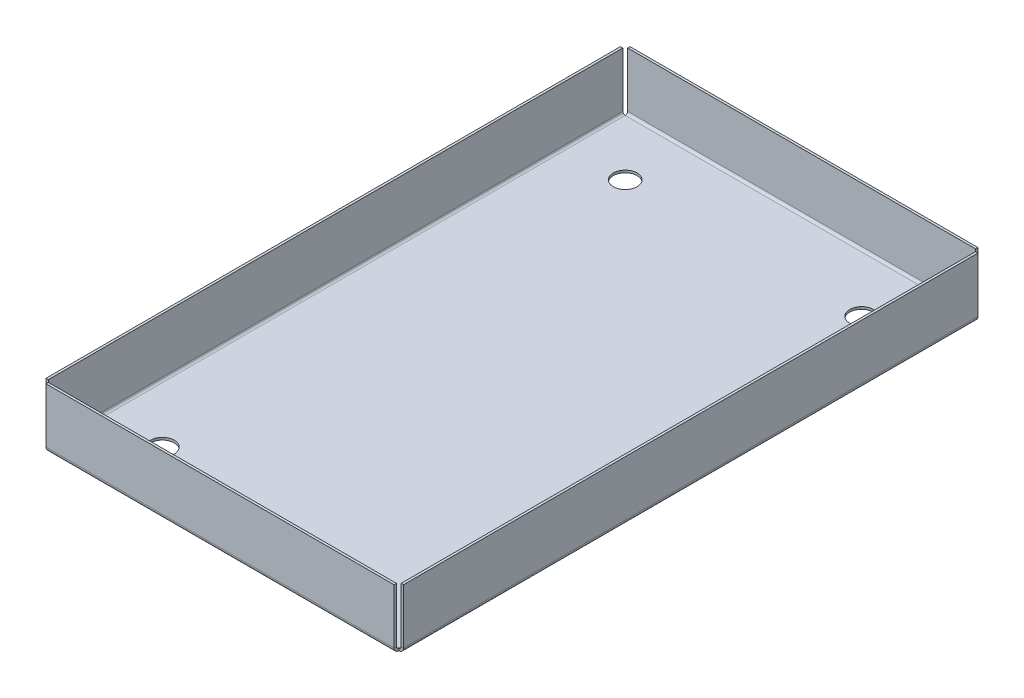
SolidWorks part; units mm, degrees
note: The reader was unsure of these and kept them because the rebuilt part matched: thickness of "Base-Flange1", "Edge-Flange1", "Edge-Flange2", "Edge-Flange3", "Edge-Flange4", "Sheet-Metal1", "Sheet-Metal2", "Sheet-Metal3", "Sheet-Metal4", "Sheet-Metal5", "Sheet-Metal6", "Sheet-Metal7", "Sheet-Metal17"; flange length of "Edge-Flange1", "Edge-Flange2", "Edge-Flange3", "Edge-Flange4".
ref_plane "Front Plane" through (0, 0, 0) normal (0, 0, 1) x (1, 0, 0)
ref_plane "Top Plane" through (0, 0, 0) normal (0, 1, 0) x (1, 0, 0)
ref_plane "Right Plane" through (0, 0, 0) normal (1, 0, 0) x (0, 0, -1)
sketch "Sketch1" plane through (0, 0, 0) normal (0, 1, 0) x (1, 0, 0)
  line L1 (-7.3, 12.05) -> (7.3, 12.05)
  line L2 (-7.3, 12.05) -> (-7.3, -12.05)
  line L3 (-7.3, -12.05) -> (7.3, -12.05)
  line L4 (7.3, 12.05) -> (7.3, -12.05)
  line L5 (-7.3, 12.05) -> (7.3, -12.05) construction
  line L6 (-7.3, -12.05) -> (7.3, 12.05) construction
  point P0 (0, 0)
  dimension "D1" = 24.1
  dimension "D2" = 14.6
base flange "Base-Flange1" sketch "Sketch1" thickness 0.1 reverse thickness direction no parameters "D1"=0.7366
edge flange "Edge-Flange1" sketch "Sketch10" flange angle 90 flange length 2.5 flange position bend outside bend radius 0.1 thickness 0.1 relief rectangular parameters "D6"=10
sketch "Sketch10" plane through (0, 0, 12.05) normal (0, 0, 1) x (1, 0, 0)
  line L0 (-7.3, 0) -> (7.3, 0) construction
  line L1 (-7.3, 0) -> (7.3, 0)
  line L2 (-7.3, 0) -> (-7.3, 2.4)
  line L3 (-7.3, 2.4) -> (7.3, 2.4)
  line L4 (7.3, 2.4) -> (7.3, 0)
bend "EdgeBend1" bend radius 0.1 bend angle 90 parameters "D5"=1
edge flange "Edge-Flange2" sketch "Sketch13" flange angle 90 flange length 2.5 flange position bend outside bend radius 0.1 thickness 0.1 relief rectangular parameters "D6"=10
sketch "Sketch13" plane through (0, 0, -12.05) normal (0, 0, -1) x (-1, 0, 0)
  line L0 (-7.3, 0) -> (7.3, 0) construction
  line L1 (-7.3, 0) -> (7.3, 0)
  line L2 (-7.3, 0) -> (-7.3, 2.4)
  line L3 (-7.3, 2.4) -> (7.3, 2.4)
  line L4 (7.3, 2.4) -> (7.3, 0)
bend "EdgeBend2" bend radius 0.1 bend angle 90 parameters "D5"=2
edge flange "Edge-Flange3" sketch "Sketch16" flange angle 90 flange length 2.5 flange position bend outside bend radius 0.1 thickness 0.1 relief rectangular parameters "D6"=10
sketch "Sketch16" plane through (7.3, 0, 0) normal (1, 0, 0) x (0, 0, -1)
  line L0 (-12.05, 0) -> (12.05, 0) construction
  line L1 (-12.05, 0) -> (12.05, 0)
  line L2 (-12.05, 0) -> (-12.05, 2.4)
  line L3 (-12.05, 2.4) -> (12.05, 2.4)
  line L4 (12.05, 2.4) -> (12.05, 0)
bend "EdgeBend3" bend radius 0.1 bend angle 90 parameters "D5"=3
edge flange "Edge-Flange4" sketch "Sketch21" flange angle 90 flange length 2.5 flange position bend outside bend radius 0.1 thickness 0.1 relief rectangular parameters "D6"=10
sketch "Sketch21" plane through (-7.3, 0, 0) normal (-1, 0, 0) x (0, 0, 1)
  line L2 (-12.05, 0) -> (-12.05, 2.4)
  line L3 (-12.05, 2.4) -> (12.05, 2.4)
  line L4 (12.05, 2.4) -> (12.05, 0)
  line L5 (-12.05, 0) -> (12.05, 0) construction
  line L6 (-12.05, 0) -> (12.05, 0)
bend "EdgeBend4" bend radius 0.1 bend angle 90 parameters "D5"=4
sketch "Sketch23" plane through (0, -0.1, 0) normal (0, -1, 0) x (1, 0, 0)
  line L0 (-7.5, 12.05) -> (-7.5, -12.05) construction
  line L1 (7.3, 12.25) -> (-7.3, 12.25) construction
  line L2 (0, 0) -> (-13.5156, 0) construction
  line L3 (0, 0) -> (0, -13.6288) construction
  circle A0 centre (-4.96, 9.71) radius 0.5
  circle A1 centre (-4.96, -9.71) radius 0.5
  circle A2 centre (4.96, -9.71) radius 0.5
  dimension "D1" = 1
  dimension "D2" = 2.54
  dimension "D3" = 2.54
extrude "Cut-Extrude1" cut sketch "Sketch23" against normal blind 10 normal cut yes
sketch "Sketch24" plane through (0, -0.1, 0) normal (0, -1, 0) x (1, 0, 0)
  line L1 (-1.7162, 8.2997) -> (-1.7162, -6.7416) construction
  line L2 (-3.9171, 8.2997) -> (-3.9171, -6.7416) construction
  text T0 "RN2483" font "Arial Narrow" height 1.4
  text T1 "########" font "Arial Narrow" height 1.2
extrude "Boss-Extrude2" add sketch "Sketch24" along normal blind 0.01 separate body
sketch "Sketch26" plane through (0, -0.1, 0) normal (0, -1, 0) x (1, 0, 0)
  line L4 (1.6101, 2.1924) -> (2.7319, 2.0303)
  line L5 (2.7724, 1.5974) -> (2.0967, 1.1781)
  line L6 (2.0967, 1.1781) -> (2.7724, 0.7858)
  line L7 (2.7319, 0.3394) -> (1.6101, 0.1636)
  line L8 (1.6101, 0.1636) -> (1.6101, 0.5288)
  line L9 (1.6101, 0.5288) -> (2.3669, 0.6235)
  line L10 (2.3669, 0.6235) -> (1.7588, 0.9752)
  line L11 (1.7588, 1.3945) -> (2.3805, 1.7462)
  line L12 (2.3805, 1.7462) -> (1.6101, 1.8409)
  line L13 (1.6101, 1.8409) -> (1.6101, 2.1924)
  line L14 (1.6101, 0.0013) -> (1.6101, -0.3098)
  line L15 (1.6101, -0.3098) -> (2.5562, -0.3098)
  line L16 (2.5562, -0.3098) -> (2.5562, 0.0013)
  line L17 (2.5562, 0.0013) -> (1.6101, 0.0013)
  line L18 (2.3129, -1.7301) -> (2.4481, -1.7301)
  line L19 (2.5697, -1.5814) -> (2.5697, -0.7968)
  line L20 (2.3399, -0.4992) -> (1.8129, -0.4992)
  line L21 (1.6101, -0.7562) -> (1.6101, -1.5814)
  line L22 (1.7588, -1.7437) -> (1.8669, -1.7437)
  line L23 (1.8669, -1.7437) -> (1.8669, -0.9188)
  line L24 (2.0021, -0.7968) -> (2.1642, -0.7968)
  line L25 (2.3129, -0.9188) -> (2.3129, -1.7301)
  line L27 (1.8534, -2.5282) -> (1.8534, -2.7311)
  line L28 (1.7588, -2.8393) -> (1.6101, -2.8393)
  line L29 (1.6101, -2.8393) -> (1.6101, -3.1234)
  line L30 (1.6101, -3.1234) -> (1.8399, -3.1234)
  line L31 (2.1372, -3.1369) -> (2.3669, -3.1369)
  line L32 (2.5697, -2.9476) -> (2.5697, -2.5282)
  line L34 (2.3264, -2.5282) -> (2.3264, -2.7852)
  line L35 (2.2453, -2.8529) -> (2.1642, -2.8529)
  line L36 (2.0967, -2.7717) -> (2.0967, -2.5282)
  line L38 (2.5697, -2.5282) -> (2.5697, -1.906)
  line L39 (2.5697, -1.906) -> (1.6101, -1.906)
  line L40 (1.6101, -1.906) -> (1.6101, -2.1901)
  line L41 (1.6101, -2.1901) -> (1.8534, -2.2036)
  line L42 (1.8534, -2.2036) -> (1.8534, -2.5282)
  line L44 (2.0967, -2.5282) -> (2.0967, -2.1901)
  line L45 (2.0967, -2.1901) -> (2.3264, -2.2036)
  line L46 (2.3264, -2.2036) -> (2.3264, -2.5282)
  line L48 (1.6101, -3.962) -> (1.6101, -4.3408)
  line L49 (1.8399, -4.6114) -> (2.3264, -4.6114)
  line L50 (2.5832, -4.3137) -> (2.5832, -3.962)
  line L52 (2.3264, -3.962) -> (2.3264, -4.1785)
  line L53 (2.2183, -4.2867) -> (1.948, -4.2867)
  line L54 (1.8669, -4.192) -> (1.8669, -3.962)
  line L56 (2.5832, -3.962) -> (2.5832, -3.5833)
  line L57 (2.3534, -3.2993) -> (1.8399, -3.2993)
  line L58 (1.6101, -3.5563) -> (1.6101, -3.962)
  line L60 (1.8669, -3.962) -> (1.8669, -3.7186)
  line L61 (1.948, -3.6239) -> (2.2183, -3.6239)
  line L62 (2.3264, -3.7591) -> (2.3264, -3.962)
  line L63 (1.9615, -7.0597) -> (1.9615, -6.478)
  line L64 (1.9615, -6.478) -> (1.975, -6.478)
  line L65 (1.975, -6.478) -> (1.6101, -6.478)
  line L66 (1.6101, -6.478) -> (1.6101, -6.1669)
  line L67 (1.6101, -6.1669) -> (2.5697, -6.1669)
  line L68 (2.5697, -6.1669) -> (2.5697, -6.478)
  line L69 (2.5697, -6.478) -> (2.2318, -6.478)
  line L70 (2.2318, -6.478) -> (2.2318, -7.0597)
  line L71 (2.2318, -7.0597) -> (2.5697, -7.0597)
  line L72 (2.5697, -7.0597) -> (2.5697, -7.3844)
  line L73 (2.5697, -7.3844) -> (1.6101, -7.3844)
  line L74 (1.6101, -7.3844) -> (1.6101, -7.0597)
  line L75 (1.6101, -7.0597) -> (1.975, -7.0597)
  line L76 (1.975, -7.0597) -> (1.9615, -7.0597)
  line L78 (1.8534, -8.6964) -> (1.8534, -9.1157)
  line L79 (2.0832, -9.3321) -> (2.3129, -9.3321)
  line L80 (2.5562, -9.0887) -> (2.5562, -8.6964)
  line L82 (2.3264, -8.6964) -> (2.3264, -8.9669)
  line L83 (2.2453, -9.0346) -> (2.1642, -9.0346)
  line L84 (2.0832, -8.9534) -> (2.0832, -8.6964)
  line L86 (2.5562, -8.6964) -> (2.5562, -8.0742)
  line L87 (2.5562, -8.0742) -> (1.6101, -8.0742)
  line L88 (1.6101, -8.0742) -> (1.6101, -8.3717)
  line L89 (1.6101, -8.3717) -> (1.8534, -8.3717)
  line L90 (1.8534, -8.3717) -> (1.8534, -8.6964)
  line L92 (2.0832, -8.6964) -> (2.0832, -8.3717)
  line L93 (2.0832, -8.3717) -> (2.3264, -8.3583)
  line L94 (2.3264, -8.3583) -> (2.3264, -8.6964)
  line L95 (2.1053, 5.4392) -> (2.7319, 5.0088)
  line L96 (2.7319, 5.0088) -> (4.7593, 6.2754)
  line L97 (4.7593, 6.7058) -> (4.1447, 7.1485)
  line L98 (4.1447, 7.1485) -> (2.1053, 5.8573)
  line L99 (1.7612, 3.9759) -> (4.1325, 5.4884)
  line L100 (4.1325, 5.4884) -> (4.7714, 5.0211)
  line L101 (4.7714, 4.6153) -> (2.7319, 3.3241)
  line L102 (3.2847, 3.2135) -> (5.5945, 4.6768)
  line L103 (2.8547, 8.0831) -> (3.8499, 7.3575)
  line L104 (3.8499, 7.3575) -> (3.0759, 6.8534)
  line L105 (2.7319, 6.8534) -> (1.8473, 7.4928)
  line L106 (2.3129, -5.9911) -> (2.4481, -5.9911)
  line L107 (2.5697, -5.8424) -> (2.5697, -5.0577)
  line L108 (2.3399, -4.7601) -> (1.8129, -4.7601)
  line L109 (1.6101, -5.0171) -> (1.5966, -5.8424)
  line L110 (1.7588, -6.0046) -> (1.8534, -6.0046)
  line L111 (1.8534, -6.0046) -> (1.8534, -5.1794)
  line L112 (1.9885, -5.0577) -> (2.1642, -5.0577)
  line L113 (2.3129, -5.1794) -> (2.3129, -5.9911)
  line L114 (1.6101, -7.5602) -> (1.6101, -7.8713)
  line L115 (1.6101, -7.8713) -> (2.5562, -7.8713)
  line L116 (2.5562, -7.8713) -> (2.5562, -7.5602)
  line L117 (2.5562, -7.5602) -> (1.6101, -7.5602)
  spline S0 degree 3 poles (2.7319, 2.0303) (2.9211, 1.9897) (2.9481, 1.7327) (2.7724, 1.5974) knots 0 0 0 0 1 1 1 1
  spline S1 degree 3 poles (2.7724, 0.7858) (2.894, 0.6776) (2.9481, 0.4747) (2.7319, 0.3394) knots 0 0 0 0 1 1 1 1
  spline S2 degree 3 poles (1.7588, 0.9752) (1.6372, 1.0561) (1.6237, 1.2863) (1.7588, 1.3945) knots 0 0 0 0 1 1 1 1
  spline S3 degree 3 poles (2.4481, -1.7301) (2.5291, -1.7301) (2.5697, -1.676) (2.5697, -1.5814) knots 0 0 0 0 1 1 1 1
  spline S4 degree 3 poles (2.5697, -0.7968) (2.5697, -0.648) (2.4345, -0.4992) (2.3399, -0.4992) knots 0 0 0 0 1 1 1 1
  spline S5 degree 3 poles (1.8129, -0.4992) (1.7453, -0.4992) (1.6101, -0.6074) (1.6101, -0.7562) knots 0 0 0 0 1 1 1 1
  spline S6 degree 3 poles (1.6101, -1.5814) (1.5966, -1.676) (1.6642, -1.7437) (1.7588, -1.7437) knots 0 0 0 0 1 1 1 1
  spline S7 degree 3 poles (1.8669, -0.9188) (1.8534, -0.8374) (1.921, -0.7968) (2.0021, -0.7968) knots 0 0 0 0 1 1 1 1
  spline S8 degree 3 poles (2.1642, -0.7968) (2.2318, -0.7968) (2.3129, -0.8509) (2.3129, -0.9188) knots 0 0 0 0 1 1 1 1
  spline S9 degree 3 poles (1.8534, -2.7311) (1.8534, -2.7852) (1.8264, -2.8258) (1.7588, -2.8393) knots 0 0 0 0 1 1 1 1
  spline S10 degree 2 poles (1.8399, -3.1234) (1.9615, -3.1234) (1.9885, -3.0017) knots 0 0 0 1 1 1
  spline S11 degree 2 poles (1.9885, -3.0017) (2.0426, -3.1234) (2.1372, -3.1369) knots 0 0 0 1 1 1
  spline S12 degree 3 poles (2.3669, -3.1369) (2.4751, -3.1234) (2.5562, -3.0289) (2.5697, -2.9476) knots 0 0 0 0 1 1 1 1
  spline S13 degree 3 poles (2.3264, -2.7852) (2.3264, -2.8123) (2.2859, -2.8529) (2.2453, -2.8529) knots 0 0 0 0 1 1 1 1
  spline S14 degree 3 poles (2.1642, -2.8529) (2.1237, -2.8529) (2.0967, -2.8258) (2.0967, -2.7717) knots 0 0 0 0 1 1 1 1
  spline S15 degree 3 poles (1.6101, -4.3408) (1.6101, -4.4625) (1.7047, -4.6114) (1.8399, -4.6114) knots 0 0 0 0 1 1 1 1
  spline S16 degree 3 poles (2.3264, -4.6114) (2.4481, -4.6114) (2.5832, -4.476) (2.5832, -4.3137) knots 0 0 0 0 1 1 1 1
  spline S17 degree 3 poles (2.3264, -4.1785) (2.3264, -4.2461) (2.2724, -4.2867) (2.2183, -4.2867) knots 0 0 0 0 1 1 1 1
  spline S18 degree 3 poles (1.948, -4.2867) (1.8804, -4.2867) (1.8669, -4.2461) (1.8669, -4.192) knots 0 0 0 0 1 1 1 1
  spline S19 degree 3 poles (2.5832, -3.5833) (2.5832, -3.4482) (2.4751, -3.2993) (2.3534, -3.2993) knots 0 0 0 0 1 1 1 1
  spline S20 degree 3 poles (1.8399, -3.2993) (1.7183, -3.2993) (1.6101, -3.4075) (1.6101, -3.5563) knots 0 0 0 0 1 1 1 1
  spline S21 degree 3 poles (1.8669, -3.7186) (1.8669, -3.6645) (1.8804, -3.6239) (1.948, -3.6239) knots 0 0 0 0 1 1 1 1
  spline S22 degree 3 poles (2.2183, -3.6239) (2.2859, -3.6239) (2.3264, -3.6915) (2.3264, -3.7591) knots 0 0 0 0 1 1 1 1
  spline S23 degree 3 poles (1.8534, -9.1157) (1.8534, -9.2104) (1.975, -9.3321) (2.0832, -9.3321) knots 0 0 0 0 1 1 1 1
  spline S24 degree 3 poles (2.3129, -9.3321) (2.4345, -9.3321) (2.5562, -9.224) (2.5562, -9.0887) knots 0 0 0 0 1 1 1 1
  spline S25 degree 3 poles (2.3264, -8.9669) (2.3264, -9.0075) (2.2859, -9.0346) (2.2453, -9.0346) knots 0 0 0 0 1 1 1 1
  spline S26 degree 3 poles (2.1642, -9.0346) (2.1237, -9.0346) (2.0832, -9.0075) (2.0832, -8.9534) knots 0 0 0 0 1 1 1 1
  spline S27 degree 2 poles (2.1053, 5.8573) (1.7612, 5.6605) (2.1053, 5.4392) knots 0 0 0 1 1 1
  spline S28 degree 2 poles (4.7593, 6.2754) (5.0294, 6.4722) (4.7593, 6.7058) knots 0 0 0 1 1 1
  spline S29 degree 3 poles (1.1224, 5.6851) (1.1224, 5.0211) (1.3681, 4.4186) (1.7612, 3.9759) knots 0 0 0 0 1 1 1 1
  spline S30 degree 2 poles (4.7714, 5.0211) (5.0294, 4.8242) (4.7714, 4.6153) knots 0 0 0 1 1 1
  spline S31 degree 3 poles (2.7319, 3.3241) (2.9039, 3.2627) (3.1004, 3.2258) (3.2847, 3.2135) knots 0 0 0 0 1 1 1 1
  spline S32 degree 3 poles (5.5945, 4.6768) (5.7174, 4.9842) (5.7911, 5.3285) (5.7911, 5.6851) knots 0 0 0 0 1 1 1 1
  spline S33 degree 3 poles (5.7911, 5.6851) (5.7911, 6.9703) (4.8041, 8.1691) (3.4567, 8.1691) knots 0 0 0 0 1 1 1 1
  spline S34 degree 3 poles (3.4567, 8.1691) (3.2479, 8.1691) (3.039, 8.1322) (2.8547, 8.0831) knots 0 0 0 0 1 1 1 1
  spline S35 degree 2 poles (3.0759, 6.8534) (2.8916, 6.7304) (2.7319, 6.8534) knots 0 0 0 1 1 1
  spline S36 degree 3 poles (1.8473, 7.4928) (1.3639, 7.009) (1.1224, 6.36) (1.1224, 5.6851) knots 0 0 0 0 1 1 1 1
  spline S37 degree 3 poles (2.4481, -5.9911) (2.5291, -5.9911) (2.5697, -5.9369) (2.5697, -5.8424) knots 0 0 0 0 1 1 1 1
  spline S38 degree 3 poles (2.5697, -5.0577) (2.5697, -4.9089) (2.4481, -4.7601) (2.3399, -4.7601) knots 0 0 0 0 1 1 1 1
  spline S39 degree 3 poles (1.8129, -4.7601) (1.7318, -4.7737) (1.6101, -4.8684) (1.6101, -5.0171) knots 0 0 0 0 1 1 1 1
  spline S40 degree 3 poles (1.5966, -5.8424) (1.5966, -5.9369) (1.6642, -6.0046) (1.7588, -6.0046) knots 0 0 0 0 1 1 1 1
  spline S41 degree 3 poles (1.8534, -5.1794) (1.8534, -5.0983) (1.9074, -5.0577) (1.9885, -5.0577) knots 0 0 0 0 1 1 1 1
  spline S42 degree 3 poles (2.1642, -5.0577) (2.2318, -5.0577) (2.3129, -5.1119) (2.3129, -5.1794) knots 0 0 0 0 1 1 1 1
extrude "Boss-Extrude1" add sketch "Sketch26" along normal blind 0.01 separate body
sketch "Bend-Lines1" plane through (0, 0, 0) normal (0, 1, 0) x (1, 0, 0)
sketch "Bounding-Box1" plane through (0, 0, 0) normal (0, 1, 0) x (1, 0, 0)
sheet metal parameters "Sheet-Metal1" thickness 0.1 parameters "D1"=0.7366
flat pattern "Flat-Pattern1" [suppressed]
sketch "Bend-Lines2" plane through (0, 0, 0) normal (0, 1, 0) x (1, 0, 0)
sketch "Bounding-Box2" [suppressed] plane through (0, 0, 0) normal (0, 1, 0) x (1, 0, 0)
sheet metal parameters "Sheet-Metal2" thickness 0.1 parameters "D1"=0.7366
flat pattern "Flat-Pattern1" [suppressed]
sketch "Bend-Lines2" plane through (0, 0, 0) normal (0, 1, 0) x (1, 0, 0)
sketch "Bounding-Box2" [suppressed] plane through (0, 0, 0) normal (0, 1, 0) x (1, 0, 0)
bend of the flat pattern "Flatten-<EdgeBend1>1"
sheet metal parameters "Sheet-Metal3" thickness 0.1 parameters "D1"=0.7366
flat pattern "Flat-Pattern1" [suppressed]
sketch "Bend-Lines2" plane through (0, 0, 0) normal (0, 1, 0) x (1, 0, 0)
sketch "Bounding-Box2" [suppressed] plane through (0, 0, 0) normal (0, 1, 0) x (1, 0, 0)
bend of the flat pattern "Flatten-<EdgeBend1>1"
bend of the flat pattern "Flatten-<EdgeBend2>1"
sheet metal parameters "Sheet-Metal4" thickness 0.1 parameters "D1"=0.7366
flat pattern "Flat-Pattern1" [suppressed]
sketch "Bend-Lines2" plane through (0, 0, 0) normal (0, 1, 0) x (1, 0, 0)
sketch "Bounding-Box2" [suppressed] plane through (0, 0, 0) normal (0, 1, 0) x (1, 0, 0)
bend of the flat pattern "Flatten-<EdgeBend1>1"
bend of the flat pattern "Flatten-<EdgeBend2>1"
bend of the flat pattern "Flatten-<EdgeBend3>1"
sheet metal parameters "Sheet-Metal5" thickness 0.1 parameters "D1"=0.7366
flat pattern "Flat-Pattern1" [suppressed]
sketch "Bend-Lines2" plane through (0, 0, 0) normal (0, 1, 0) x (1, 0, 0)
sketch "Bounding-Box2" [suppressed] plane through (0, 0, 0) normal (0, 1, 0) x (1, 0, 0)
bend of the flat pattern "Flatten-<EdgeBend1>1"
bend of the flat pattern "Flatten-<EdgeBend2>1"
bend of the flat pattern "Flatten-<EdgeBend3>1"
bend of the flat pattern "Flatten-<EdgeBend4>1"
sheet metal parameters "Sheet-Metal6" thickness 0.1 parameters "D1"=0.7366
flat pattern "Flat-Pattern1" [suppressed]
sketch "Bend-Lines2" plane through (0, 0, 0) normal (0, 1, 0) x (1, 0, 0)
sketch "Bounding-Box2" [suppressed] plane through (0, 0, 0) normal (0, 1, 0) x (1, 0, 0)
bend of the flat pattern "Flatten-<EdgeBend1>1"
bend of the flat pattern "Flatten-<EdgeBend2>1"
bend of the flat pattern "Flatten-<EdgeBend3>1"
bend of the flat pattern "Flatten-<EdgeBend4>1"
sheet metal parameters "Sheet-Metal7" thickness 0.1 parameters "D1"=0.7366
flat pattern "Flat-Pattern1" [suppressed]
sketch "Bend-Lines2" plane through (0, 0, 0) normal (0, 1, 0) x (1, 0, 0)
sketch "Bounding-Box2" [suppressed] plane through (0, 0, 0) normal (0, 1, 0) x (1, 0, 0)
bend of the flat pattern "Flatten-<EdgeBend1>1"
bend of the flat pattern "Flatten-<EdgeBend2>1"
bend of the flat pattern "Flatten-<EdgeBend3>1"
bend of the flat pattern "Flatten-<EdgeBend4>1"
sheet metal parameters "Sheet-Metal17" thickness 0.1 parameters "D1"=0.7366
flat pattern "Flat-Pattern1" [suppressed]
sketch "Bend-Lines2" plane through (0, 0, 0) normal (0, 1, 0) x (1, 0, 0)
sketch "Bounding-Box2" [suppressed] plane through (0, 0, 0) normal (0, 1, 0) x (1, 0, 0)
bend of the flat pattern "Flatten-<EdgeBend1>1"
bend of the flat pattern "Flatten-<EdgeBend2>1"
bend of the flat pattern "Flatten-<EdgeBend3>1"
bend of the flat pattern "Flatten-<EdgeBend4>1"
